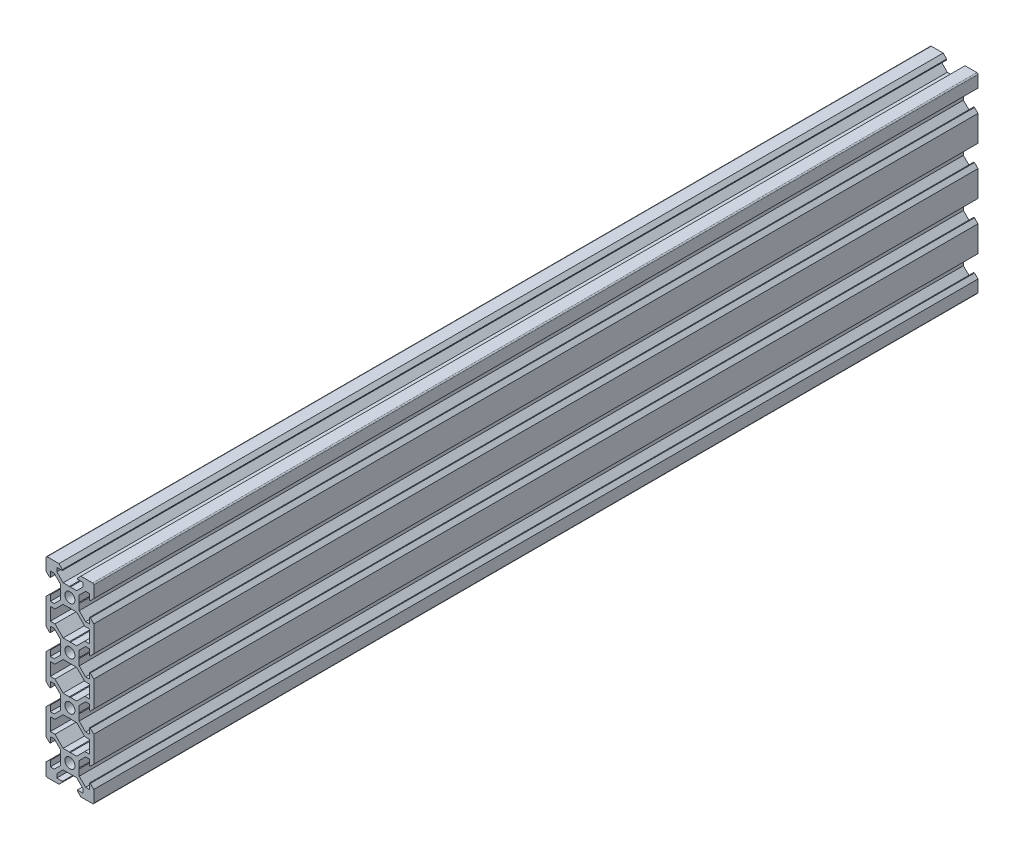
SolidWorks part; units mm, degrees
ref_plane "Plan de face" through (0, 0, 0) normal (0, 0, 1) x (1, 0, 0)
ref_plane "Plan de dessus" through (0, 0, 0) normal (0, 1, 0) x (1, 0, 0)
ref_plane "Plan de droite" through (0, 0, 0) normal (1, 0, 0) x (0, 0, -1)
ref_axis "Axe" through (0, 0, -13.782) along (0, 0, 1)
sketch "Esquisse1" plane through (0, 0, 0) normal (0, 0, 1) x (1, 0, 0)
  line L0 (0, 27.6392) -> (0, -27.6392) construction
  line L1 (-33.6074, 0) -> (33.6074, 0) construction
  line L2 (0, 0) -> (-22.2114, 22.2114) construction
  line L3 (-9.5, 10) -> (-4.58, 10)
  line L4 (-4.58, 10) -> (-3.125, 8.545)
  line L5 (-3.125, 8.545) -> (-3.125, 8.2)
  line L6 (-3.125, 8.2) -> (-5.5, 8.2)
  line L7 (-2.8393, 3.9) -> (-5.5, 6.5607)
  line L8 (-2.8393, 3.9) -> (-0.21, 3.9)
  line L9 (-5.5, 6.5607) -> (-5.5, 8.2)
  line L10 (0, 3.69) -> (0, 2.1)
  line L11 (-3.9, 2.8393) -> (-6.5607, 5.5)
  line L12 (-8.545, 3.125) -> (-8.2, 3.125)
  line L13 (-8.2, 3.125) -> (-8.2, 5.5)
  line L14 (-6.5607, 5.5) -> (-8.2, 5.5)
  line L15 (-10, 4.58) -> (-8.545, 3.125)
  line L16 (-10, 9.5) -> (-10, 4.58)
  line L17 (-0.21, 3.9) -> (0, 3.69)
  line L18 (-3.9, 2.8393) -> (-3.9, 0.21)
  line L19 (-6.2393, -12.7) -> (-8.2, -12.7)
  line L20 (-3.9, 0.21) -> (-3.69, 0)
  line L21 (-0.21, -3.9) -> (0, -3.69)
  line L22 (0, -3.69) -> (0, -2.1)
  line L23 (-6.5607, -5.5) -> (-8.2, -5.5)
  line L24 (-2.8393, -3.9) -> (-0.21, -3.9)
  line L25 (-8.545, -3.125) -> (-8.2, -3.125)
  line L26 (-10, -4.58) -> (-8.545, -3.125)
  line L27 (-8.2, -3.125) -> (-8.2, -5.5)
  line L28 (-2.8393, -3.9) -> (-6.2393, -7.3)
  line L29 (-3.9, -2.8393) -> (-6.5607, -5.5)
  line L30 (-3.9, -2.8393) -> (-3.9, -0.21)
  line L31 (-3.9, -0.21) -> (-3.69, 0)
  line L32 (-6.2393, -7.3) -> (-8.2, -7.3)
  line L33 (-8.2, -7.3) -> (-8.2, -12.7)
  line L34 (-8.2, -10) -> (-10, -10) construction
  line L35 (-10, -15.42) -> (-10, -4.58)
  line L36 (-3.9, -19.79) -> (-3.69, -20)
  line L37 (-3.9, -17.1607) -> (-3.9, -19.79)
  line L38 (-3.9, -17.1607) -> (-6.5607, -14.5)
  line L39 (-2.8393, -16.1) -> (-6.2393, -12.7)
  line L40 (-8.2, -16.875) -> (-8.2, -14.5)
  line L41 (-10, -15.42) -> (-8.545, -16.875)
  line L42 (-8.545, -16.875) -> (-8.2, -16.875)
  line L43 (-2.8393, -16.1) -> (-0.21, -16.1)
  line L44 (-6.5607, -14.5) -> (-8.2, -14.5)
  line L45 (0, -16.31) -> (0, -17.9)
  line L46 (-0.21, -16.1) -> (0, -16.31)
  line L47 (-8.2, -30) -> (-10, -30) construction
  line L48 (-3.69, -20) -> (0, -20) construction
  line L49 (-0.21, -23.9) -> (0, -23.69)
  line L50 (0, -23.69) -> (0, -22.1)
  line L51 (-6.5607, -25.5) -> (-8.2, -25.5)
  line L52 (-2.8393, -23.9) -> (-0.21, -23.9)
  line L53 (-8.545, -23.125) -> (-8.2, -23.125)
  line L54 (-10, -24.58) -> (-8.545, -23.125)
  line L55 (-8.2, -23.125) -> (-8.2, -25.5)
  line L56 (-2.8393, -23.9) -> (-6.2393, -27.3)
  line L57 (-3.9, -22.8393) -> (-6.5607, -25.5)
  line L58 (-3.9, -22.8393) -> (-3.9, -20.21)
  line L59 (-3.9, -20.21) -> (-3.69, -20)
  line L60 (-10, -24.58) -> (-10, -35.42)
  line L61 (-8.2, -32.7) -> (-8.2, -27.3)
  line L62 (-3.69, -40) -> (0, -40) construction
  line L63 (-8.2, -50) -> (-10, -50) construction
  line L64 (0, -60) -> (-22.2114, -82.2114) construction
  line L65 (-33.6074, -60) -> (33.6074, -60) construction
  line L66 (0, -87.6392) -> (0, -32.3608) construction
  line L67 (-6.2393, -32.7) -> (-8.2, -32.7)
  line L68 (-3.9, -39.79) -> (-3.69, -40)
  line L69 (-3.9, -37.1607) -> (-3.9, -39.79)
  line L70 (-3.9, -37.1607) -> (-6.5607, -34.5)
  line L71 (-2.8393, -36.1) -> (-6.2393, -32.7)
  line L72 (-8.2, -36.875) -> (-8.2, -34.5)
  line L73 (-10, -35.42) -> (-8.545, -36.875)
  line L74 (-8.545, -36.875) -> (-8.2, -36.875)
  line L75 (-6.2393, -27.3) -> (-8.2, -27.3)
  line L76 (-2.8393, -36.1) -> (-0.21, -36.1)
  line L77 (-6.5607, -34.5) -> (-8.2, -34.5)
  line L78 (0, -36.31) -> (0, -37.9)
  line L79 (-0.21, -36.1) -> (0, -36.31)
  line L80 (-0.21, -43.9) -> (0, -43.69)
  line L81 (0, -43.69) -> (0, -42.1)
  line L82 (-6.5607, -45.5) -> (-8.2, -45.5)
  line L83 (-2.8393, -43.9) -> (-0.21, -43.9)
  line L84 (-8.545, -43.125) -> (-8.2, -43.125)
  line L85 (-10, -44.58) -> (-8.545, -43.125)
  line L86 (-8.2, -43.125) -> (-8.2, -45.5)
  line L87 (-2.8393, -43.9) -> (-6.2393, -47.3)
  line L88 (-3.9, -42.8393) -> (-6.5607, -45.5)
  line L89 (-3.9, -42.8393) -> (-3.9, -40.21)
  line L90 (-3.9, -40.21) -> (-3.69, -40)
  line L91 (-10, -44.58) -> (-10, -55.42)
  line L92 (-8.2, -52.7) -> (-8.2, -47.3)
  line L93 (-6.2393, -52.7) -> (-8.2, -52.7)
  line L94 (-3.9, -59.79) -> (-3.69, -60)
  line L95 (-3.9, -57.1607) -> (-3.9, -59.79)
  line L96 (-3.9, -57.1607) -> (-6.5607, -54.5)
  line L97 (-2.8393, -56.1) -> (-6.2393, -52.7)
  line L98 (-8.2, -56.875) -> (-8.2, -54.5)
  line L99 (-10, -55.42) -> (-8.545, -56.875)
  line L100 (-8.545, -56.875) -> (-8.2, -56.875)
  line L101 (-2.8393, -56.1) -> (-0.21, -56.1)
  line L102 (-6.5607, -54.5) -> (-8.2, -54.5)
  line L103 (0, -56.31) -> (0, -57.9)
  line L104 (-0.21, -56.1) -> (0, -56.31)
  line L105 (-3.9, -60.21) -> (-3.69, -60)
  line L106 (-6.2393, -47.3) -> (-8.2, -47.3)
  line L107 (-3.9, -62.8393) -> (-3.9, -60.21)
  line L108 (-0.21, -63.9) -> (0, -63.69)
  line L109 (-10, -69.5) -> (-10, -64.58)
  line L110 (-10, -64.58) -> (-8.545, -63.125)
  line L111 (-6.5607, -65.5) -> (-8.2, -65.5)
  line L112 (-8.2, -63.125) -> (-8.2, -65.5)
  line L113 (-8.545, -63.125) -> (-8.2, -63.125)
  line L114 (-3.9, -62.8393) -> (-6.5607, -65.5)
  line L115 (0, -63.69) -> (0, -62.1)
  line L116 (-5.5, -66.5607) -> (-5.5, -68.2)
  line L117 (-2.8393, -63.9) -> (-0.21, -63.9)
  line L118 (-2.8393, -63.9) -> (-5.5, -66.5607)
  line L119 (-3.125, -68.2) -> (-5.5, -68.2)
  line L120 (-3.125, -68.545) -> (-3.125, -68.2)
  line L121 (-4.58, -70) -> (-3.125, -68.545)
  line L122 (-9.5, -70) -> (-4.58, -70)
  arc A0 (0, -2.1) -> (0, 2.1) centre (0, 0) cw
  arc A1 (-9.5, 10) -> (-10, 9.5) centre (-9.5, 9.5) ccw
  arc A2 (0, -42.1) -> (0, -37.9) centre (0, -40) cw
  arc A3 (-9.5, -70) -> (-10, -69.5) centre (-9.5, -69.5) cw
  arc A4 (0, -17.9) -> (0, -22.1) centre (0, -20) ccw
  arc A5 (0, -57.9) -> (0, -62.1) centre (0, -60) ccw
  point P4 (0, 0)
  point P7 (0, 0)
  point P30 (-10, 10)
  point P60 (0, -20)
  point P146 (-10, -70)
  dimension "D5" = 11
  dimension "D2" = 2.1
  dimension "D3" = 6.25
  dimension "D10" = 0.5
  dimension "D4" = 9.16
  dimension "D6" = 1.5
  dimension "D7" = 1.8
  dimension "D8" = 4.3
  dimension "D9" = 20
  dimension "D11" = 0.42
  dimension "D12" = 10
  dimension "D13" = 1.8
extrude "Boss.-Extru.1" add sketch "Esquisse1" along normal blind 370
sketch "Esquisse3" plane through (0, 0, 370) normal (0, 0, 1) x (1, 0, 0)
  line L0 (0, 0) -> (-9.8536, 9.8536) construction
  line L1 (-8.2, 8.2) -> (-8.2, 6.57)
  line L2 (-8.2, 6.57) -> (-7.54, 6.57)
  line L3 (-7.54, 6.57) -> (-6.57, 7.54)
  line L4 (-8.2, 3.125) -> (-8.2, 5.5) construction
  line L5 (-6.57, 8.2) -> (-6.57, 7.54)
  line L6 (-8.2, 8.2) -> (-6.57, 8.2)
  line L7 (-5.5, 6.5607) -> (-5.5, 8.2) construction
  line L8 (-10, -30) -> (6.918, -30) construction
  line L9 (-10, -24.58) -> (-10, -35.42) construction
  line L10 (-8.2, -68.2) -> (-6.57, -68.2)
  line L11 (-6.57, -68.2) -> (-6.57, -67.54)
  line L12 (-7.54, -66.57) -> (-6.57, -67.54)
  line L13 (-8.2, -66.57) -> (-7.54, -66.57)
  line L14 (-8.2, -68.2) -> (-8.2, -66.57)
  arc A0 (-9.5, 10) -> (-10, 9.5) centre (-9.5, 9.5) ccw construction
  point P13 (-7.055, 7.055)
  point P14 (-6.57, 7.87)
  point P26 (-7.055, -67.055)
  dimension "D1" = 1.07
extrude "Enlèv. mat.-Extru.1" [suppressed] cut sketch "Esquisse3" against normal through all
mirror "Symétrie1" about plane through (0, 3.69, 370) normal (-1, 0, 0) of "Enlèv. mat.-Extru.1", "Boss.-Extru.1"
